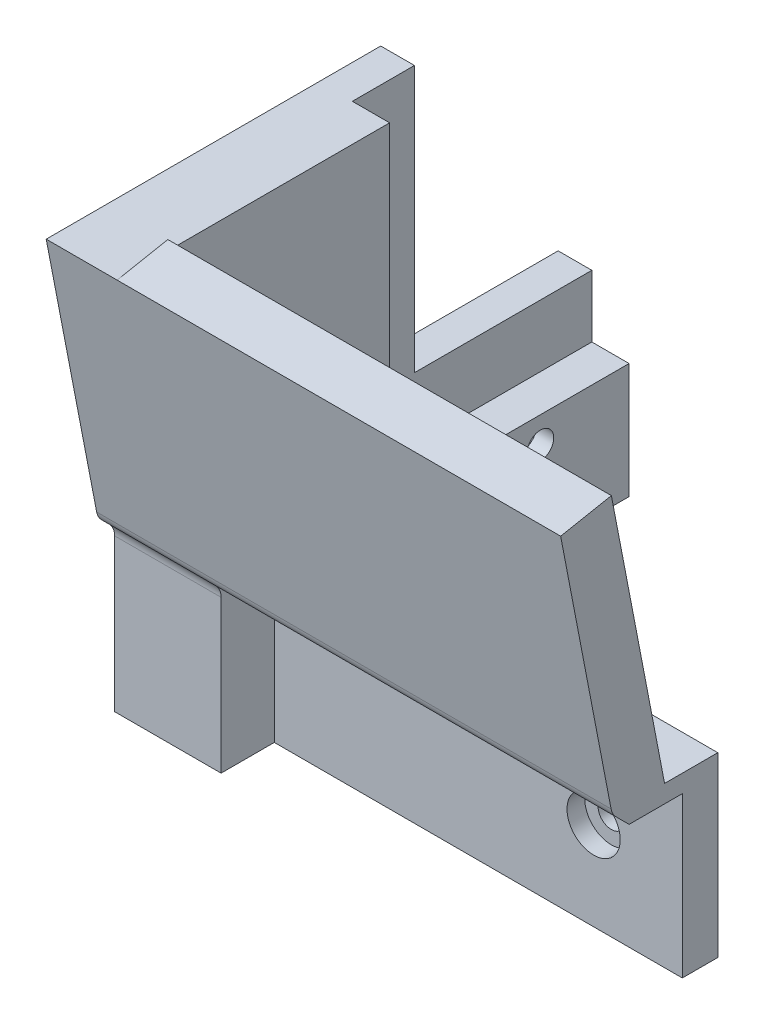
SolidWorks part; units mm, degrees
ref_plane "前视基准面" through (0, 0, 0) normal (0, 0, 1) x (1, 0, 0)
ref_plane "上视基准面" through (0, 0, 0) normal (0, 1, 0) x (1, 0, 0)
ref_plane "右视基准面" through (0, 0, 0) normal (1, 0, 0) x (0, 0, -1)
other "Configuration Table"
sketch "草图1" plane through (0, 0, 0) normal (1, 0, 0) x (0, 0, -1)
  line L0 (0, 0) -> (-10, 0)
  line L1 (-10, 0) -> (-17.7164, 40)
  line L2 (-17.7164, 40) -> (-12, 41.1027)
  line L3 (-12, 41.1027) -> (-6, 10)
  line L4 (-6, 10) -> (0, 10)
  line L5 (0, 10) -> (0, 0)
  dimension "D1" = 10
  dimension "D2" = 6
  dimension "D3" = 10
  dimension "D4" = 6
  dimension "D5" = 40
extrude "凸台-拉伸1" add sketch "草图1" along normal blind 50
sketch "草图2" plane through (0, 0, 0) normal (0, -1, 0) x (1, 0, 0)
  line L4 (0, 10) -> (0, 0)
  line L5 (0, 0) -> (50, 0)
  line L6 (50, 0) -> (50, 10)
  line L7 (50, 10) -> (0, 10)
  line L8 (0, 10) -> (0, 0)
  line L9 (0, 0) -> (50, 0)
  line L10 (50, 0) -> (50, 10)
  line L11 (50, 10) -> (0, 10)
  dimension "D1" = 0
extrude "凸台-拉伸2" add sketch "草图2" along normal blind 10
sketch "草图3" plane through (0, 0, 0) normal (-1, 0, 0) x (0, 0, 1)
  line L1 (0, 10) -> (10, 10)
  line L2 (0, 10) -> (0, -10)
  line L3 (0, -10) -> (10, -10)
  line L4 (10, 10) -> (10, -10)
extrude "凸台-拉伸3" add sketch "草图3" along normal blind 20
sketch "草图4" plane through (0, 10, 0) normal (0, 1, 0) x (1, 0, 0)
  line L1 (-20, 0) -> (0, 0)
  line L2 (-20, 0) -> (-20, -10)
  line L3 (-20, -10) -> (0, -10)
  line L4 (0, 0) -> (0, -10)
extrude "凸台-拉伸4" add sketch "草图4" along normal blind 30
sketch "草图5" plane through (50, 0, 0) normal (1, 0, 0) x (0, 0, -1)
  line L0 (-10, 10) -> (-11.9291, 10)
  line L1 (-17.7164, 40) -> (-10, 0) construction
  line L2 (-11.9291, 10) -> (-10, 0)
  line L3 (-10, 0) -> (-10, 10)
extrude "切除-拉伸1" cut sketch "草图5" against normal up to surface (50 mm away) up to face at (0, 27.9595, 12.4291)
chamfer "倒角1" distance 2 angle 45 1 edges at (25, 10, 10)
sketch "草图9" plane through (0, 0, 10) normal (0, 0, 1) x (1, 0, 0)
  line L0 (-20, 40) -> (-10, 40) construction
  line L1 (-20, 40) -> (0, 40) construction
  line L2 (-10, 40) -> (-10, 20) construction
  line L3 (50, -10) -> (50, 0) construction
  line L4 (50, -10) -> (50, 8) construction
  line L5 (50, 0) -> (40, 0) construction
  circle A0 centre (-10, 20) radius 1.5
  circle A1 centre (40, 0) radius 1.5
  dimension "D3" = 3
  dimension "D5" = 3
  dimension "D1" = 10
  dimension "D2" = 20
  dimension "D4" = 10
extrude "切除-拉伸2" cut sketch "草图9" against normal through all
sketch "草图12" plane through (0, 0, 10) normal (0, 0, 1) x (1, 0, 0)
  line L6 (0, 30.7352) -> (0, 40)
  line L7 (0, 30.7352) -> (0, 40)
  line L8 (0, 40) -> (-20, 40)
  line L9 (50, -10) -> (50, 8)
  line L10 (50, 8) -> (0, 8)
  line L11 (0, 8) -> (0, 30.7352)
  line L15 (50, -10) -> (50, 8)
  line L16 (50, 8) -> (0, 8)
  line L17 (0, 8) -> (0, 30.7352)
  line L19 (0, 40) -> (-20, 40)
  line L20 (-20, 40) -> (-20, -10)
  line L21 (-20, 40) -> (-20, -10)
  line L22 (-20, -10) -> (50, -10)
  line L23 (-20, -10) -> (50, -10)
  dimension "D1" = 0
extrude "切除-拉伸4" cut sketch "草图12" against normal blind 6
sketch "草图13" plane through (0, 8, 0) normal (0, -1, 0) x (1, 0, 0)
  line L0 (50, 4) -> (0, 4) construction
  line L1 (0, 10) -> (4, 10)
  line L2 (0, 10) -> (0, 4)
  line L3 (0, 4) -> (4, 4)
  line L4 (4, 10) -> (4, 4)
  line L6 (50, 10) -> (46, 10)
  line L7 (50, 10) -> (50, 4)
  line L8 (50, 4) -> (46, 4)
  line L9 (46, 10) -> (46, 4)
  dimension "D1" = 4
  dimension "D2" = 4
extrude "凸台-拉伸12" add sketch "草图13" along normal up to surface (18 mm away) up to face at (15, -10, 2)
fillet "圆角2" radius 2 3 edges at (25, 9.9121, 11.9121) (48, 8, 10) (2, 8, 10)
sketch "草图14" plane through (0, 0, 4) normal (0, 0, 1) x (1, 0, 0)
  line L0 (-20, -10) -> (0, -10) construction
  line L1 (-20, 40) -> (-4, 40)
  line L2 (-20, 40) -> (-20, -10)
  line L3 (-20, -10) -> (-4, -10)
  line L4 (-4, 40) -> (-4, -10)
  dimension "D1" = 16
extrude "切除-拉伸5" cut sketch "草图14" against normal blind 10
sketch "草图16" plane through (0, 0, 0) normal (1, 0, 0) x (0, 0, -1)
  line L0 (0, 10) -> (-6, 10)
  line L1 (-6, 10) -> (-7.9291, 20)
  line L2 (-6, 10) -> (-12, 41.1027) construction
  line L3 (-7.9291, 20) -> (0, 20)
  line L4 (0, 40) -> (0, 10) construction
  line L5 (0, 20) -> (0, 10)
  dimension "D1" = 10
extrude "凸台-拉伸14" add sketch "草图16" along normal blind 10
sketch "草图17" plane through (0, 0, 0) normal (0, 0, -1) x (-1, 0, 0)
  line L1 (0, 40) -> (4, 40)
  line L2 (0, 40) -> (0, -10)
  line L3 (0, -10) -> (4, -10)
  line L4 (4, 40) -> (4, -10)
extrude "凸台-拉伸15" add sketch "草图17" along normal blind 20
sketch "草图20" plane through (-4, 0, 0) normal (-1, 0, 0) x (0, 0, 1)
  line L0 (4, 20) -> (7.9291, 20) construction
  line L1 (4, 12) -> (-20, 12)
  line L2 (4, 12) -> (4, -10)
  line L3 (4, -10) -> (-20, -10)
  line L4 (-20, 12) -> (-20, -10)
  dimension "D1" = 8
extrude "切除-拉伸8" cut sketch "草图20" against normal up to surface (4 mm away) up to face at (0, 13.687, 9.9675)
sketch "草图21" plane through (0, 0, 4) normal (0, 0, 1) x (1, 0, 0)
  line L5 (-4, 12) -> (0, 12)
  line L6 (0, 12) -> (0, 20)
  line L7 (0, 20) -> (0, 40)
  line L8 (0, 40) -> (-4, 40)
  line L9 (-4, 40) -> (-4, 12)
  line L10 (-4, 12) -> (0, 12)
  line L11 (0, 12) -> (0, 20)
  line L12 (0, 20) -> (0, 40)
  line L13 (0, 40) -> (-4, 40)
  line L14 (-4, 40) -> (-4, 12)
  dimension "D1" = 0
extrude "凸台-拉伸16" add sketch "草图21" along normal up to surface (13.7164 mm away) up to face at (25, 25.257, 14.8723)
sketch "草图22" plane through (0, 12, 0) normal (0, -1, 0) x (1, 0, 0)
  line L1 (0, 0) -> (-4, 0)
  line L2 (0, 0) -> (0, 12.3149)
  line L3 (0, 12.3149) -> (-4, 12.3149)
  line L4 (-4, 0) -> (-4, 12.3149)
extrude "凸台-拉伸17" add sketch "草图22" along normal up to surface (22 mm away) up to face at (25, -10, 6)
sketch "草图23" plane through (0, 0, 0) normal (1, 0, 0) x (0, 0, -1)
  line L5 (-12.0283, 10.5141) -> (-12.3149, 12)
  line L6 (-12.3149, 12) -> (-12.3149, -10)
  line L7 (-12.3149, -10) -> (-10, -10)
  line L8 (-10, -10) -> (-10, 7.1716)
  line L9 (-10.5858, 8.5858) -> (-11.4787, 9.4787)
  line L10 (-12.0283, 10.5141) -> (-12.3149, 12)
  line L11 (-12.3149, 12) -> (-12.3149, -10)
  line L12 (-12.3149, -10) -> (-10, -10)
  line L13 (-10, -10) -> (-10, 7.1716)
  line L14 (-10.5858, 8.5858) -> (-11.4787, 9.4787)
  arc A2 (-12.0283, 10.5141) -> (-11.4787, 9.4787) centre (-10.0645, 10.8929) ccw
  arc A3 (-10, 7.1716) -> (-10.5858, 8.5858) centre (-12, 7.1716) ccw
  arc A4 (-12.0283, 10.5141) -> (-11.4787, 9.4787) centre (-10.0645, 10.8929) ccw
  arc A5 (-10, 7.1716) -> (-10.5858, 8.5858) centre (-12, 7.1716) ccw
  dimension "D1" = 0
extrude "切除-拉伸9" cut sketch "草图23" against normal up to surface (4 mm away) up to face at (-4, 13.7143, 0.3352)
sketch "草图24" plane through (46, 0, 0) normal (-1, 0, 0) x (0, 0, 1)
  line L5 (4, -10) -> (10, -10)
  line L6 (10, -10) -> (10, 7.1716)
  line L7 (10.5858, 8.5858) -> (10, 8)
  line L8 (10, 8) -> (4, 8)
  line L9 (4, 8) -> (4, -10)
  line L10 (4, -10) -> (10, -10)
  line L11 (10, -10) -> (10, 7.1716)
  line L12 (10.5858, 8.5858) -> (10, 8)
  line L13 (10, 8) -> (4, 8)
  line L14 (4, 8) -> (4, -10)
  arc A1 (10.5858, 8.5858) -> (10, 7.1716) centre (12, 7.1716) ccw
  arc A2 (10.5858, 8.5858) -> (10, 7.1716) centre (12, 7.1716) ccw
  dimension "D1" = 0
extrude "切除-拉伸10" cut sketch "草图24" against normal up to surface (4 mm away) up to face at (50, 11.687, 8.9746)
sketch "草图25" plane through (0, 0, 4) normal (0, 0, 1) x (1, 0, 0)
  circle A0 centre (40, 0) radius 3
  dimension "D1" = 6
extrude "切除-拉伸11" cut sketch "草图25" against normal offset from surface (2 mm away) 2 up to face at (41.5, 0, 0)
sketch "草图26" plane through (10, 0, 0) normal (1, 0, 0) x (0, 0, -1)
  line L4 (0, 10) -> (0, 20)
  line L5 (0, 20) -> (-7.9291, 20)
  line L6 (-7.9291, 20) -> (-6, 10)
  line L7 (-6, 10) -> (0, 10)
  line L8 (0, 10) -> (0, 20)
  line L9 (0, 20) -> (-7.9291, 20)
  line L10 (-7.9291, 20) -> (-6, 10)
  line L11 (-6, 10) -> (0, 10)
  dimension "D1" = 0
extrude "切除-拉伸12" cut sketch "草图26" against normal blind 10
sketch "草图27" plane through (-4, 0, 0) normal (-1, 0, 0) x (0, 0, 1)
  line L0 (-20, 40) -> (-20, 12)
  line L1 (-20, 12) -> (-20, 40) construction
  line L8 (0, -10) -> (10, -10)
  line L9 (10, -10) -> (10, 7.1716)
  line L10 (10.5858, 8.5858) -> (11.4787, 9.4787)
  line L11 (12.0283, 10.5141) -> (17.7164, 40)
  line L12 (17.7164, 40) -> (-20, 40)
  line L13 (-20, 40) -> (-20, 12)
  line L14 (-20, 12) -> (0, 12)
  line L15 (0, 12) -> (0, -10)
  line L16 (0, -10) -> (10, -10)
  line L17 (10, -10) -> (10, 7.1716)
  line L18 (10.5858, 8.5858) -> (11.4787, 9.4787)
  line L19 (12.0283, 10.5141) -> (17.7164, 40)
  line L20 (17.7164, 40) -> (-20, 40)
  line L22 (-20, 12) -> (0, 12)
  line L23 (0, 12) -> (0, -10)
  arc A2 (10.5858, 8.5858) -> (10, 7.1716) centre (12, 7.1716) ccw
  arc A3 (11.4787, 9.4787) -> (12.0283, 10.5141) centre (10.0645, 10.8929) ccw
  arc A4 (10.5858, 8.5858) -> (10, 7.1716) centre (12, 7.1716) ccw
  arc A5 (11.4787, 9.4787) -> (12.0283, 10.5141) centre (10.0645, 10.8929) ccw
  dimension "D2" = 0
  dimension "D1" = 0
extrude "凸台-拉伸19" add sketch "草图27" along normal blind 4
sketch "草图34" plane through (0, 12, 0) normal (0, -1, 0) x (1, 0, 0)
  line L4 (0, 0) -> (-8, 0)
  line L5 (-8, 0) -> (-8, -20)
  line L6 (-8, -20) -> (0, -20)
  line L7 (0, -20) -> (0, 0)
  line L8 (0, 0) -> (-8, 0)
  line L9 (-8, 0) -> (-8, -20)
  line L10 (-8, -20) -> (0, -20)
  line L11 (0, -20) -> (0, 0)
  dimension "D1" = 0
extrude "凸台-拉伸21" add sketch "草图34" along normal up to surface (22 mm away) up to face at (15.3333, -10, 4.6667)
sketch "草图35" plane through (0, 0, -20) normal (0, 0, -1) x (-1, 0, 0)
  line L0 (0, -10) -> (0, 10) construction
  line L1 (8, -10) -> (0, -10)
  line L2 (8, -10) -> (8, 10)
  line L3 (8, 10) -> (0, 10)
  line L4 (0, -10) -> (0, 10)
  dimension "D1" = 20
extrude "凸台-拉伸22" add sketch "草图35" along normal blind 20
sketch "草图28" plane through (0, 0, 0) normal (1, 0, 0) x (0, 0, -1)
  line L1 (20, 40) -> (13, 40)
  line L2 (20, 40) -> (20, 10)
  line L3 (20, 3) -> (13, 3)
  line L4 (13, 40) -> (13, 3)
  line L5 (40, 10) -> (20, 10) construction
  line L6 (40, 10) -> (40, -10) construction
  line L7 (20, 3) -> (40, 3)
  line L9 (20, 10) -> (40, 10)
  line L10 (40, 3) -> (40, 10)
  dimension "D1" = 7
  dimension "D2" = 7
extrude "切除-拉伸18" cut sketch "草图28" against normal blind 4.2
sketch "草图38" plane through (-8, 0, 0) normal (-1, 0, 0) x (0, 0, 1)
  line L0 (-40, 0) -> (-30, 0) construction
  line L1 (-40, -10) -> (-40, 10) construction
  circle A0 centre (-30, 0) radius 1.5
  dimension "D2" = 3
  dimension "D1" = 10
extrude "切除-拉伸19" cut sketch "草图38" against normal through all
sketch "草图39" plane through (-8, 0, 0) normal (-1, 0, 0) x (0, 0, 1)
  circle A0 centre (-30, 0) radius 2.9
  dimension "D1" = 5.8
extrude "切除-拉伸20" cut sketch "草图39" against normal offset from surface (6 mm away) 2 up to face at (0, 0, -28.5)
